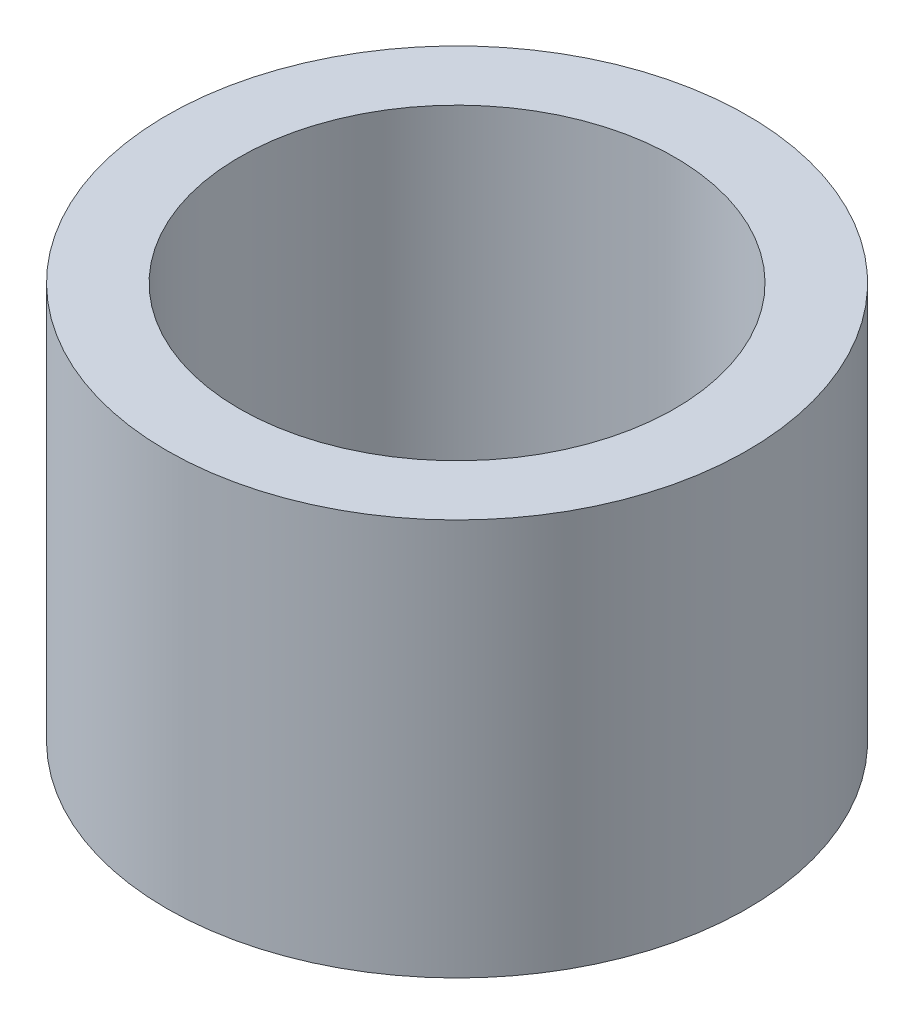
SolidWorks part; units mm, degrees
ref_plane "Front Plane" through (0, 0, 0) normal (0, 0, 1) x (1, 0, 0)
ref_plane "Top Plane" through (0, 0, 0) normal (0, 1, 0) x (1, 0, 0)
ref_plane "Right Plane" through (0, 0, 0) normal (1, 0, 0) x (0, 0, -1)
sketch "Sketch1" plane through (0, 0, 0) normal (0, 1, 0) x (1, 0, 0)
  circle A0 centre (0, 0) radius 25
  dimension "SLEEVE_OD" = 50
extrude "Boss-Extrude1" add sketch "Sketch1" along normal blind 34.1587
sketch "Sketch2" plane through (0, 0, 0) normal (0, 1, 0) x (1, 0, 0)
  circle A0 centre (0, 0) radius 18.7549
  dimension "BORE_D" = 37.5098
extrude "Cut-Extrude1" cut sketch "Sketch2" along normal through all
chamfer "Chamfer1" distance 2.9838 angle 56.521 rebuild error yes
